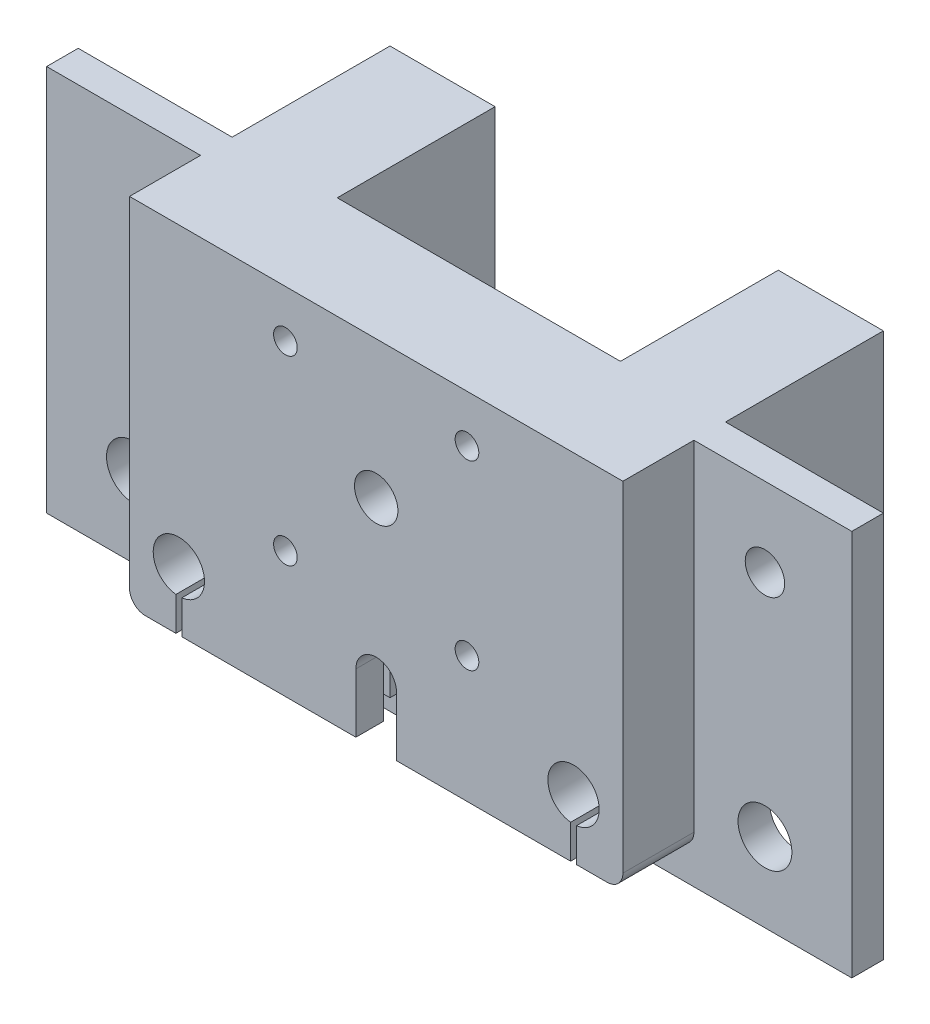
SolidWorks part; units mm, degrees
ref_plane "Front Plane" through (0, 0, 0) normal (0, 0, 1) x (1, 0, 0)
ref_plane "Top Plane" through (0, 0, 0) normal (0, 1, 0) x (1, 0, 0)
ref_plane "Right Plane" through (0, 0, 0) normal (1, 0, 0) x (0, 0, -1)
sketch "Sketch1" plane through (0, 0, 0) normal (0, 0, 1) x (1, 0, 0)
  line L1 (-31.25, 0) -> (31.25, 0)
  line L2 (-31.25, 0) -> (-31.25, 45)
  line L3 (-31.25, 45) -> (31.25, 45)
  line L4 (31.25, 0) -> (31.25, 45)
  point P4 (0, 0)
  dimension "D1" = 62.5
  dimension "D2" = 45
extrude "Boss-Extrude1" add sketch "Sketch1" along normal blind 20
sketch "Sketch2" plane through (0, 0, 20) normal (0, 0, 1) x (1, 0, 0)
  line L0 (31.25, 45) -> (-31.25, 45) construction
  line L1 (-18.75, 45) -> (18.75, 45)
  line L2 (-18.75, 45) -> (-18.75, 0)
  line L3 (-18.75, 0) -> (18.75, 0)
  line L4 (18.75, 45) -> (18.75, 0)
  line L5 (-31.25, 0) -> (31.25, 0) construction
  point P8 (0, 0)
  dimension "D1" = 37.5
extrude "Cut-Extrude1" cut sketch "Sketch2" against normal offset from surface (5 mm away) 15 up to face at (0, 22.5, 0)
sketch "Sketch3" plane through (0, 0, 0) normal (0, 0, -1) x (-1, 0, 0)
  line L0 (0, 45) -> (0, 0) construction
  line L3 (-31.25, 45) -> (31.25, 45) construction
  circle A0 centre (0, 27.5) radius 11.5
  dimension "D1" = 23
  dimension "D2" = 17.5
extrude "Cut-Extrude2" cut sketch "Sketch3" against normal blind 2
sketch "Sketch4" plane through (0, 0, 0) normal (0, 0, -1) x (-1, 0, 0)
  circle A0 centre (11.5, 39) radius 1.5
  circle A1 centre (0, 27.5) radius 11.5 construction
  circle A2 centre (0, 27.5) radius 11.5 construction
  dimension "D3" = 3
  dimension "D1" = 11.5
  dimension "D2" = 11.5
extrude "Cut-Extrude3" cut sketch "Sketch4" against normal up to surface (15 mm away) up to face at (0, 22.5, 15)
pattern_circular "CirPattern1" count 4 over 360 about axis through (0, 27.5, 0) along (0, 0, -1) of "Cut-Extrude3"
sketch "Sketch5" plane through (0, 0, 2) normal (0, 0, -1) x (-1, 0, 0)
  circle A0 centre (0, 27.5) radius 2.75
  dimension "D1" = 5.5
extrude "Cut-Extrude4" cut sketch "Sketch5" against normal through all
sketch "Sketch8" plane through (0, 0, 0) normal (0, 0, -1) x (-1, 0, 0)
  line L0 (0, 0) -> (0, 45) construction
  line L1 (7.125, 0) -> (-7.125, 0)
  line L2 (7.125, 0) -> (7.125, 11.75)
  line L3 (5.125, 13.75) -> (-5.125, 13.75)
  line L4 (-7.125, 0) -> (-7.125, 11.75)
  line L5 (-31.25, 45) -> (31.25, 45) construction
  line L6 (31.25, 0) -> (-31.25, 0) construction
  arc A1 (-5.125, 13.75) -> (-7.125, 11.75) centre (-5.125, 11.75) ccw
  arc A2 (7.125, 11.75) -> (5.125, 13.75) centre (5.125, 11.75) ccw
  point P9 (0, 0)
  point P17 (-7.125, 13.75)
  point P20 (7.125, 13.75)
  dimension "D3" = 2
  dimension "D1" = 14.25
  dimension "D2" = 13.75
extrude "Cut-Extrude7" cut sketch "Sketch8" against normal blind 3 from offset 6.5 offset against normal yes
sketch "Sketch9" plane through (0, 0, 0) normal (0, 0, -1) x (-1, 0, 0)
  line L0 (4.75, 7.5) -> (4.75, 0)
  line L1 (31.25, 0) -> (-31.25, 0) construction
  line L2 (4.75, 0) -> (-4.75, 0)
  line L3 (-4.75, 0) -> (-4.75, 7.5)
  line L6 (25, 7.5) -> (-25, 7.5) construction
  arc A0 (-4.75, 7.5) -> (4.75, 7.5) centre (0, 7.5) cw
  dimension "D1" = 4.75
  dimension "D2" = 7.5
extrude "Cut-Extrude8" cut sketch "Sketch9" against normal up to surface (6.5 mm away) up to face at (0, 8.6381, 6.5)
sketch "Sketch10" plane through (0, 0, 15) normal (0, 0, 1) x (1, 0, 0)
  line L0 (2.575, 7.5) -> (2.575, 0)
  line L1 (-18.75, 0) -> (18.75, 0) construction
  line L2 (2.575, 0) -> (-2.575, 0)
  line L3 (-2.575, 0) -> (-2.575, 7.5)
  line L4 (25, 7.5) -> (-25, 7.5) construction
  arc A0 (-2.575, 7.5) -> (2.575, 7.5) centre (0, 7.5) cw
  dimension "D1" = 2.575
  dimension "D2" = 7.5
  dimension "D3" = 50
extrude "Cut-Extrude9" cut sketch "Sketch10" against normal up to surface (5.5 mm away) up to face at (0, 8.6381, 9.5)
sketch "Sketch11" plane through (31.25, 0, 0) normal (1, 0, 0) x (0, 0, -1)
  line L0 (-20, 0) -> (0, 0) construction
  line L1 (-20, 0) -> (-20, 45) construction
  circle A0 centre (-17.5, 2.5) radius 1.375
  dimension "D1" = 2.75
  dimension "D2" = 2.5
  dimension "D3" = 2.5
extrude "Cut-Extrude10" cut sketch "Sketch11" against normal through all
fillet "Fillet1" radius 2 2 edges at (-31.25, 0, 10) (31.25, 0, 10)
sketch "Sketch12" plane through (31.25, 0, 0) normal (1, 0, 0) x (0, 0, -1)
  circle A0 centre (-17.5, 2.5) radius 3.625
  dimension "D1" = 7.25
extrude "Cut-Extrude12" cut sketch "Sketch12" against normal blind 3
mirror "Mirror3" about plane through (0, 0, 0) normal (1, 0, 0) of "Cut-Extrude12"
sketch "Sketch13" plane through (0, 0, 0) normal (0, 0, -1) x (-1, 0, 0)
  line L0 (29.25, 0) -> (4.75, 0) construction
  line L1 (17.9399, 0) -> (29.25, 0)
  line L2 (17.9399, 0) -> (17.9399, 45)
  line L3 (17.9399, 45) -> (31.25, 45)
  line L4 (31.25, 2) -> (31.25, 45)
  arc A0 (31.25, 2) -> (29.25, 0) centre (29.25, 2) cw
  dimension "D1" = 2
extrude "Boss-Extrude2" add sketch "Sketch13" along normal blind 20
sketch "Sketch14" plane through (-31.25, 0, 0) normal (-1, 0, 0) x (0, 0, 1)
  line L0 (14.875, 0) -> (-20, 0) construction
  line L3 (-20.25, 2.5) -> (-20.25, -1.1785)
  line L4 (-20.25, -1.1785) -> (-17.8212, -1.1785)
  line L5 (-20, 2) -> (-20, 45) construction
  circle A0 centre (-6.25, 2.5) radius 4
  circle A1 centre (-16.25, 2.5) radius 4
  line M6 (-20, 45) -> (-20, 2)
  line M7 (-20, 2) -> (13.9096, 2)
  dimension "D2" = 8
  dimension "D1" = 2.5
  dimension "D3" = 2.5
  dimension "D4" = 10
  dimension "D5" = 3.75
extrude "Cut-Extrude18" cut sketch "Sketch14" against normal blind 2 contours A1 M6 M7 | A1 M7 M6 | A1 L3 L4 | A0 region at (-31.25, -0.3234, -19.5854) region at (-31.25, 0.5658, -16.3134) region at (-31.25, 3.9452, -16.2026)
sketch "Sketch15" plane through (0, 0, 20) normal (0, 0, 1) x (1, 0, 0)
  line L1 (31.25, 45) -> (-31.25, 45)
  line L2 (31.25, 45) -> (31.25, 0)
  line L3 (31.25, 0) -> (-31.25, 0)
  line L4 (-31.25, 45) -> (-31.25, 0)
extrude "Cut-Extrude19" cut sketch "Sketch15" against normal blind 7
sketch "Sketch16" plane through (0, 0, 13) normal (0, 0, 1) x (1, 0, 0)
  line L1 (-24.625, 4.2717) -> (-24.625, 0)
  line L2 (-29.25, 0) -> (-2.575, 0) construction
  line L3 (-24.625, 0) -> (-25.375, 0)
  line L4 (-25.375, 0) -> (-25.375, 4.2717)
  line L5 (-31.25, 45) -> (-31.25, 2) construction
  circle A0 centre (-25, 7.5) radius 3.25
  circle A1 centre (0, 27.5) radius 2.75 construction
  line M5 (-29.25, 0) -> (-2.575, 0)
  dimension "D1" = 20
  dimension "D2" = 6.5
  dimension "D3" = 6.25
  dimension "D4" = 0.75
  dimension "D5" = 0.375
extrude "Cut-Extrude20" cut sketch "Sketch16" against normal through all contours A0 L4 L1 M5 | A0 region at (-25, 2.1286, 13) region at (-25, 7.5, 13)
mirror "Mirror4" about plane through (0, 0, 0) normal (1, 0, 0) of "Cut-Extrude20", "Boss-Extrude2", "Cut-Extrude18"
sketch "Sketch17" plane through (-29.25, 0, 0) normal (-1, 0, 0) x (0, 0, 1)
  circle A0 centre (-6.25, 2.5) radius 1.375
  circle A1 centre (-16.25, 2.5) radius 1.375
  dimension "D1" = 2.75
extrude "Cut-Extrude21" cut sketch "Sketch17" against normal through all
sketch "Sketch18" plane through (0, 0, 0) normal (0, 0, -1) x (-1, 0, 0)
  line L0 (-51.25, 45) -> (-31.25, 45)
  line L1 (-31.25, 45) -> (-31.25, 2)
  line L2 (-51.25, 45) -> (-51.25, -4)
  line L3 (-51.25, -4) -> (-25.375, -4)
  line L4 (50.75, -4) -> (50.75, 45)
  line L5 (50.75, 45) -> (31.25, 45)
  line L6 (31.25, 45) -> (31.25, 2)
  line L7 (29.25, 0) -> (25.375, 0)
  line L8 (-4.75, 0) -> (-4.75, -4)
  line L9 (4.75, 0) -> (4.75, -4)
  line L10 (-4.75, 0) -> (-24.625, 0)
  line L11 (4.75, -4) -> (24.625, -4)
  line L12 (24.625, 0) -> (24.625, -4)
  line L13 (25.375, 0) -> (25.375, -4)
  line L14 (24.625, 0) -> (4.75, 0)
  line L15 (25.375, -4) -> (50.75, -4)
  line L16 (-25.375, 0) -> (-25.375, -4)
  line L17 (-24.625, 0) -> (-24.625, -4)
  line L18 (-25.375, 0) -> (-29.25, 0)
  line L19 (-24.625, -4) -> (-4.75, -4)
  arc A0 (-31.25, 2) -> (-29.25, 0) centre (-29.25, 2) ccw
  arc A1 (31.25, 2) -> (29.25, 0) centre (29.25, 2) cw
extrude "Boss-Extrude3" add sketch "Sketch18" against normal blind 4
sketch "Sketch19" plane through (0, 0, 0) normal (0, 0, -1) x (-1, 0, 0)
  line L0 (-51.25, 45) -> (-51.25, -4) construction
  line L1 (-51.25, -4) -> (-25.375, -4) construction
  line L2 (50.75, -4) -> (50.75, 45) construction
  line L3 (17.9399, 45) -> (-17.9399, 45) construction
  circle A0 centre (-40.25, 6) radius 3.41
  circle A1 centre (39.75, 6) radius 3.41
  circle A2 centre (-40.25, 35) radius 2.5
  dimension "D1" = 6.82
  dimension "D6" = 5
  dimension "D2" = 11
  dimension "D3" = 10
  dimension "D4" = 11
  dimension "D5" = 10
extrude "Cut-Extrude22" cut sketch "Sketch19" against normal blind 10
equation "\"Printed Hole Size\"= 6.5"
equation "\"CAD Hole Size\"= 0.9683 * \"Printed Hole Size\" + 0.5265"
